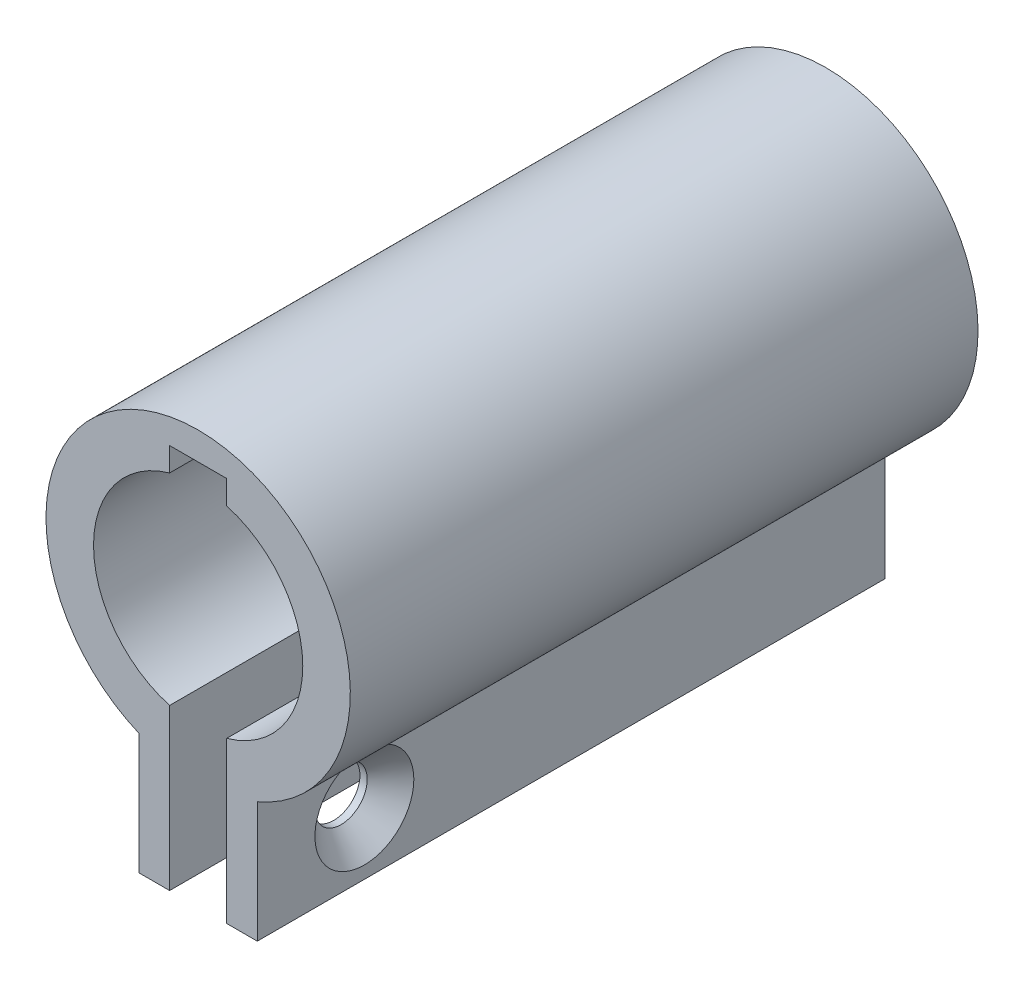
SolidWorks part; units mm, degrees
ref_plane "Front Plane" through (0, 0, 0) normal (0, 0, 1) x (1, 0, 0)
ref_plane "Top Plane" through (0, 0, 0) normal (0, 1, 0) x (1, 0, 0)
ref_plane "Right Plane" through (0, 0, 0) normal (1, 0, 0) x (0, 0, -1)
sketch "Sketch1" plane through (0, 0, 0) normal (0, 0, 1) x (1, 0, 0)
  circle A0 centre (0, 0) radius 11
  circle A1 centre (0, 0) radius 16
  dimension "D1" = 22
  dimension "D2" = 5
extrude "Boss-Extrude1" add sketch "Sketch1" along normal blind 33 and the other way blind 33
sketch "Sketch2" plane through (0, 0, 33) normal (0, 0, 1) x (1, 0, 0)
  line L0 (-3, 10.583) -> (-3, 13.083)
  line L2 (3, 13.083) -> (3, 10.583)
  line L3 (0, 0) -> (0, 13.083) construction
  line L4 (-3, 13.083) -> (0, 13.083)
  line L5 (0, 13.083) -> (3, 13.083)
  line L6 (-3, 10.583) -> (3, 10.583)
  circle A3 centre (0, 0) radius 11 construction
  dimension "D1" = 3
  dimension "D2" = 3
  dimension "D3" = 2.5
  dimension "D4" = 2.5
extrude "Cut-Extrude1" cut sketch "Sketch2" against normal blind 33
mirror "Mirror2" about plane through (0, 0, 0) normal (0, 0, -1) of "Cut-Extrude1"
sketch "Sketch3" plane through (0, 0, 33) normal (0, 0, 1) x (1, 0, 0)
  line L0 (-3, -10.583) -> (-3, -15.7162)
  line L1 (-3, -15.7162) -> (-3, -10.583)
  line L2 (3, -10.583) -> (3, -15.7162)
  line L3 (-3, -10.583) -> (3, -10.583)
  line L4 (-3, -15.7162) -> (-3, -27.4422)
  line L5 (-3, -27.4422) -> (-6.2184, -27.4422)
  line L6 (-6.2184, -27.4422) -> (-6.2184, -14.7422)
  line L7 (-6.2184, -14.7422) -> (-3, -14.7422)
  line L8 (3, -15.7162) -> (3, -27.4422)
  line L9 (3, -27.4422) -> (6.2184, -27.4422)
  line L10 (6.2184, -27.4422) -> (6.2184, -14.7422)
  line L11 (6.2184, -14.7422) -> (3, -14.7422)
  arc A0 (-3, 10.583) -> (3, 10.583) centre (0, 0) ccw construction
  circle A1 centre (0, 0) radius 16 construction
  circle M6 centre (0, 0) radius 16
  dimension "D1" = 12.7
extrude "Boss-Extrude2" add sketch "Sketch3" against normal through all contours L6 L5 L4 M6 | L9 L10 L8 M6 region at (-4.6307, -21.3633, 33) region at (4.6307, -21.3633, 33)
sketch "Sketch4" plane through (0, 0, 33) normal (0, 0, 1) x (1, 0, 0)
  line L0 (-3, -10.583) -> (-3, -16.2715)
  line L1 (-3, -10.583) -> (3, -10.583)
  line L2 (3, -10.583) -> (3, -15.7162)
  line L3 (-3, -15.7162) -> (-3, -27.4422) construction
  line L4 (-3, -16.2715) -> (3, -16.2715)
  line L5 (3, -15.7162) -> (3, -27.4422) construction
  line L6 (3, -16.2715) -> (3, -15.7162)
  arc A0 (-3, 10.583) -> (3, 10.583) centre (0, 0) ccw construction
extrude "Cut-Extrude4" cut sketch "Sketch4" against normal through all
sketch "Sketch6" plane through (6.2184, 0, 0) normal (1, 0, 0) x (0, 0, -1)
  circle A0 centre (-21.7389, -20.9335) radius 1.42
  dimension "D1" = 2.84
hole_wizard "CSK for M5 Flat Head Machine Screw1" positions "Sketch7" profile "Sketch8" countersink size "M5" standard "ANSI Metric" end condition up to next
sketch "Sketch7" plane through (6.2184, 0, 0) normal (1, 0, 0) x (0, 0, -1)
  point P0 (-21.7389, -20.9335)
sketch "Sketch8" plane through (6.2184, -20.9335, 21.7389) normal (0, 1, 0) x (0, 0, -1)
  line L0 (0, 0) -> (0, 3.2184)
  line L1 (0, 3.2184) -> (2.75, 3.2184)
  line L2 (2.75, 3.2184) -> (2.75, 2.45)
  line L3 (2.75, 2.45) -> (5.2, 0)
  line L5 (5.2, 0) -> (0, 0)
  line L6 (-2.75, 2.45) -> (-5.2, 0) construction
  line L11 (0, -6.35) -> (0, 107.95) construction
  dimension "Thru Hole Dia." = 5.5
  dimension "Thru Hole Depth" = 3.2184
  dimension "Near C'Sink Dia." = 10.4
  dimension "Near C'Sink Angle" = 90
